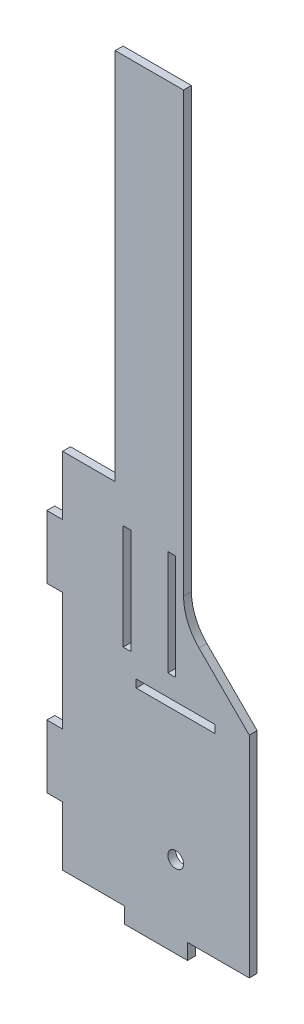
SolidWorks part; units mm, degrees
ref_plane "Front Plane" through (0, 0, 0) normal (0, 0, 1) x (1, 0, 0)
ref_plane "Top Plane" through (0, 0, 0) normal (0, 1, 0) x (1, 0, 0)
ref_plane "Right Plane" through (0, 0, 0) normal (1, 0, 0) x (0, 0, -1)
sketch "Sketch1" plane through (0, 0, 0) normal (0, 0, 1) x (1, 0, 0)
  line L0 (-71, 138) -> (-71, 0)
  line L1 (-71, 0) -> (0, 0)
  line L2 (0, 0) -> (0, 77)
  line L3 (0, 77) -> (-31, 77)
  line L4 (-31, 77) -> (-31, 138)
  line L5 (-31, 138) -> (-71, 138)
  dimension "D1" = 77
  dimension "D2" = 71
  dimension "D3" = 40
  dimension "D4" = 138
extrude "BaseShape" add sketch "Sketch1" along normal blind 3
sketch "Sketch2" plane through (0, 0, 3) normal (0, 0, 1) x (1, 0, 0)
  line L1 (-71, 0) -> (0, 0) construction
  line L2 (0, 0) -> (0, 77) construction
  circle A0 centre (-28, 25) radius 3
  dimension "D1" = 6
  dimension "D2" = 28
  dimension "D3" = 25
extrude "ShaftHoles" cut sketch "Sketch2" against normal through all
sketch "Sketch4" plane through (0, 0, 3) normal (0, 0, 1) x (1, 0, 0)
  line L0 (-31, 77) -> (-31, 138) construction
  line L1 (0, 77) -> (-31, 77)
  line L2 (0, 77) -> (0, 80)
  line L3 (0, 80) -> (-31, 80) construction
  line L4 (-31, 77) -> (-31, 80)
  line L5 (-71, 138) -> (-71, 0) construction
  line L6 (-71, 115.5) -> (-77, 115.5)
  line L7 (-71, 115.5) -> (-71, 91.5)
  line L8 (-71, 91.5) -> (-77, 91.5)
  line L9 (-77, 115.5) -> (-77, 91.5)
  line L10 (-71, 0) -> (0, 0) construction
  line L11 (-71, 46.5) -> (-77, 46.5)
  line L12 (-71, 46.5) -> (-71, 22.5)
  line L13 (-71, 22.5) -> (-77, 22.5)
  line L14 (-77, 46.5) -> (-77, 22.5)
  line L15 (-47.5, 0) -> (-23.5, 0)
  line L16 (-47.5, 0) -> (-47.5, -6)
  line L17 (-47.5, -6) -> (-23.5, -6)
  line L18 (-23.5, 0) -> (-23.5, -6)
  line L19 (-71, 115.5) -> (-71, 138) construction
  line L20 (-71, 22.5) -> (-71, 0) construction
  line L21 (-71, 69) -> (-71, 91.5) construction
  line L22 (-71, 46.5) -> (-71, 69) construction
  line L23 (-71, 0) -> (-71, 69) construction
  line L24 (-47.5, 0) -> (-71, 0) construction
  line L25 (-23.5, 0) -> (0, 0) construction
  line L26 (-25, 80) -> (0, 80)
  line L27 (-31, 138) -> (-25, 138)
  line L28 (-31, 138) -> (-31, 80)
  line L29 (-31, 80) -> (-25, 80) construction
  line L30 (-25, 138) -> (-25, 80)
  point P23 (-71, 69)
  point P28 (-71, 34.5)
  point P32 (-71, 34.5)
  dimension "D1" = 3
  dimension "D2" = 6
  dimension "D3" = 24
  dimension "D4" = 6
extrude "Fingers" add sketch "Sketch4" against normal up to surface (3 mm away) up to face at (-25, 25, 0)
sketch "Sketch5" plane through (0, 0, 3) normal (0, 0, 1) x (1, 0, 0)
  line L0 (0, 0) -> (0, 80) construction
  line L1 (-43, 77) -> (-13, 77)
  line L2 (-43, 77) -> (-43, 74)
  line L3 (-43, 74) -> (-13, 74)
  line L4 (-13, 77) -> (-13, 74)
  line L7 (-48, 125) -> (-45, 125)
  line L8 (-48, 125) -> (-48, 85)
  line L9 (-48, 85) -> (-45, 85)
  line L10 (-45, 125) -> (-45, 85)
  line L11 (0, 80) -> (-25, 80) construction
  line L12 (-25, 80) -> (-25, 138) construction
  line L13 (-31, 125) -> (-28, 125)
  line L14 (-31, 125) -> (-31, 85)
  line L15 (-31, 85) -> (-28, 85)
  line L16 (-28, 125) -> (-28, 85)
  point P20 (-29.5, 85)
  dimension "D1" = 3
  dimension "D2" = 3
  dimension "D3" = 30
  dimension "D4" = 13
  dimension "D5" = 14
  dimension "D6" = 3
  dimension "D7" = 3
  dimension "D8" = 3
  dimension "D9" = 40
  dimension "D10" = 8
extrude "Grooves" cut sketch "Sketch5" against normal through all
chamfer "Chamfer1" distance 25 angle 45 1 edges at (-25, 80, 1.5)
fillet "Fillet2" radius 20 1 edges at (-25, 105, 1.5)
sketch "Sketch6" plane through (0, 138, 0) normal (0, 1, 0) x (1, 0, 0)
  line L0 (-25, -3) -> (-71, -3) construction
  line L1 (-25, 0) -> (-51, 0)
  line L2 (-25, 0) -> (-25, -3)
  line L3 (-25, -3) -> (-51, -3)
  line L4 (-51, 0) -> (-51, -3)
  dimension "D1" = 20
extrude "MarbleChute" add sketch "Sketch6" along normal blind 142
